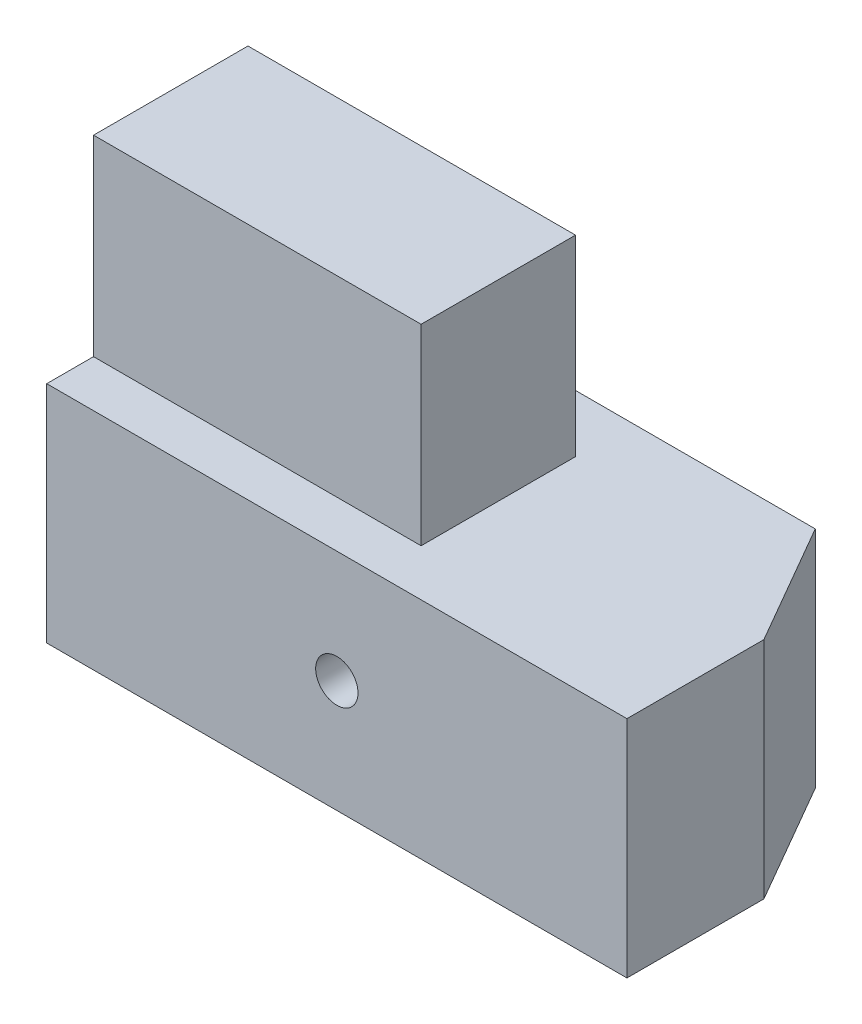
SolidWorks part; units mm, degrees
ref_plane "Front Plane" through (0, 0, 0) normal (0, 0, 1) x (1, 0, 0)
ref_plane "Top Plane" through (0, 0, 0) normal (0, 1, 0) x (1, 0, 0)
ref_plane "Right Plane" through (0, 0, 0) normal (1, 0, 0) x (0, 0, -1)
sketch "Sketch1" plane through (0, 0, 0) normal (0, 0, 1) x (1, 0, 0)
  line L0 (-62, 0) -> (62, 0) construction
  line L1 (-62, 24) -> (62, 24)
  line L2 (-62, 24) -> (-62, -24)
  line L3 (-62, -24) -> (62, -24)
  line L4 (62, 24) -> (62, -24)
  circle A0 centre (0, 0) radius 4.525
  dimension "D1" = 9.05
  dimension "D2" = 62
  dimension "D3" = 62
  dimension "D4" = 48
extrude "Boss-Extrude1" add sketch "Sketch1" against normal blind 55.25
sketch "Sketch2" plane through (0, 24, 0) normal (0, 1, 0) x (1, 0, 0)
  line L0 (62, 0) -> (-62, 0) construction
  line L1 (-61.99, 43) -> (8.01, 43)
  line L2 (-61.99, 43) -> (-61.99, 10)
  line L3 (-61.99, 10) -> (8.01, 10)
  line L4 (8.01, 43) -> (8.01, 10)
  line L5 (-62, 55.25) -> (-62, 0) construction
  dimension "D1" = 70
  dimension "D2" = 33
  dimension "D3" = 10
  dimension "D4" = 0.01
extrude "Boss-Extrude2" add sketch "Sketch2" along normal blind 41
chamfer "Chamfer1" distance 15 angle 60 1 edges at (62, 0, -55.25) first distance on face at (4.525, 0, -55.25)
